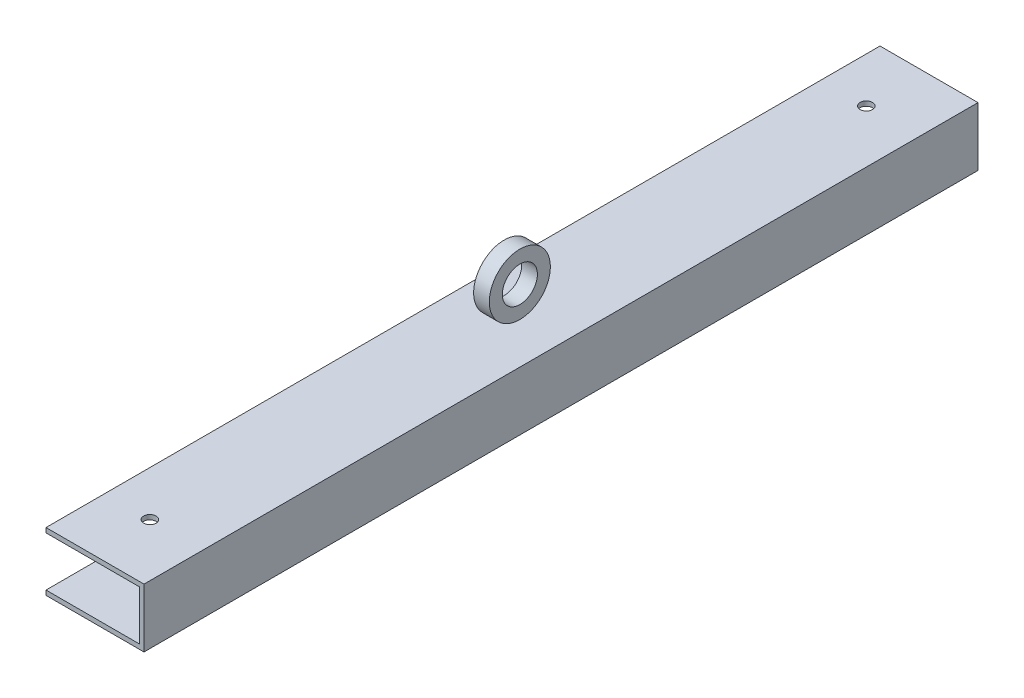
SolidWorks part; units mm, degrees
material "AISI 1020 Acero laminado en frío"
ref_plane "Alzado" through (0, 0, 0) normal (0, 0, 1) x (1, 0, 0)
ref_plane "Planta" through (0, 0, 0) normal (0, 1, 0) x (1, 0, 0)
ref_plane "Vista lateral" through (0, 0, 0) normal (1, 0, 0) x (0, 0, -1)
sketch "Croquis2" plane through (0, 0, 0) normal (0, 0, 1) x (1, 0, 0)
  line L1 (50, -30) -> (-50, -30)
  line L2 (50, -30) -> (50, 30)
  line L3 (50, 30) -> (-50, 30)
  line L4 (-50, -30) -> (-50, 30)
  line L5 (50, -30) -> (-50, 30) construction
  line L6 (50, 30) -> (-50, -30) construction
  point P0 (0, 0)
  point P6 (0, 30)
  dimension "D1" = 60
  dimension "D2" = 100
extrude "Saliente-Extruir1" add sketch "Croquis2" along normal mid plane 851
sketch "Croquis6" plane through (0, 0, 425.5) normal (0, 0, 1) x (1, 0, 0)
  line L4 (-50, 30) -> (-50, -30)
  line L5 (-50, -30) -> (50, -30)
  line L6 (50, -30) -> (50, 30)
  line L7 (50, 30) -> (-50, 30)
  line L8 (-50, 30) -> (-50, -30)
  line L9 (-50, -30) -> (50, -30)
  line L10 (50, -30) -> (50, 30)
  line L11 (50, 30) -> (-50, 30)
  line L16 (-45.2375, 25.2375) -> (-45.2375, -25.2375)
  line L17 (-45.2375, -25.2375) -> (45.2375, -25.2375)
  line L18 (45.2375, -25.2375) -> (45.2375, 25.2375)
  line L19 (45.2375, 25.2375) -> (-45.2375, 25.2375)
  line L20 (-45.2375, 25.2375) -> (-45.2375, -25.2375)
  line L21 (-45.2375, -25.2375) -> (45.2375, -25.2375)
  line L22 (45.2375, -25.2375) -> (45.2375, 25.2375)
  line L23 (45.2375, 25.2375) -> (-45.2375, 25.2375)
  dimension "D1" = 0
  dimension "D2" = 4.7625
extrude "Cortar-Extruir1" cut sketch "Croquis6" against normal blind 900 contours L22 L23 L20 L21 region at (0, 0, 425.5)
sketch "Croquis7" plane through (-50, 0, 0) normal (-1, 0, 0) x (0, 0, 1)
  line L0 (-425.5, 30) -> (-425.5, -30) construction
  line L1 (425.5, -25.2375) -> (-425.5, -25.2375)
  line L2 (425.5, -25.2375) -> (425.5, 25.2375)
  line L3 (425.5, 25.2375) -> (-425.5, 25.2375)
  line L4 (-425.5, -25.2375) -> (-425.5, 25.2375)
  line L5 (425.5, -25.2375) -> (-425.5, 25.2375) construction
  line L6 (425.5, 25.2375) -> (-425.5, -25.2375) construction
  line L7 (425.5, -30) -> (-425.5, -30) construction
  point P0 (0, 0)
  dimension "D1" = 4.7625
extrude "Cortar-Extruir2" cut sketch "Croquis7" against normal blind 20
sketch "Croquis8" plane through (0, 30, 0) normal (0, 1, 0) x (1, 0, 0)
  line L0 (-121.5247, 0) -> (93.3442, 0) construction
  line L1 (0, 497.4221) -> (0, -494.6167) construction
  line L4 (50, 425.5) -> (-50, 425.5) construction
  circle A0 centre (-4, 365.5) radius 6.35
  circle A1 centre (-4, -365.5) radius 6.35
  dimension "D1" = 12.7
  dimension "D2" = 60
  dimension "D3" = 4
extrude "Cortar-Extruir3" cut sketch "Croquis8" against normal blind 80
sketch "Croquis9" plane through (0, 0, 0) normal (1, 0, 0) x (0, 0, -1)
  line L0 (0, -85.0417) -> (0, 153.8885) construction
  line L1 (-425.5, 30) -> (425.5, 30) construction
  circle A0 centre (0, 61.15) radius 31.15
  circle A1 centre (0, 61.15) radius 17.9
  dimension "D1" = 62.3
  dimension "D2" = 35.8
extrude "Saliente-Extruir2" add sketch "Croquis9" along normal mid plane 16 separate body
